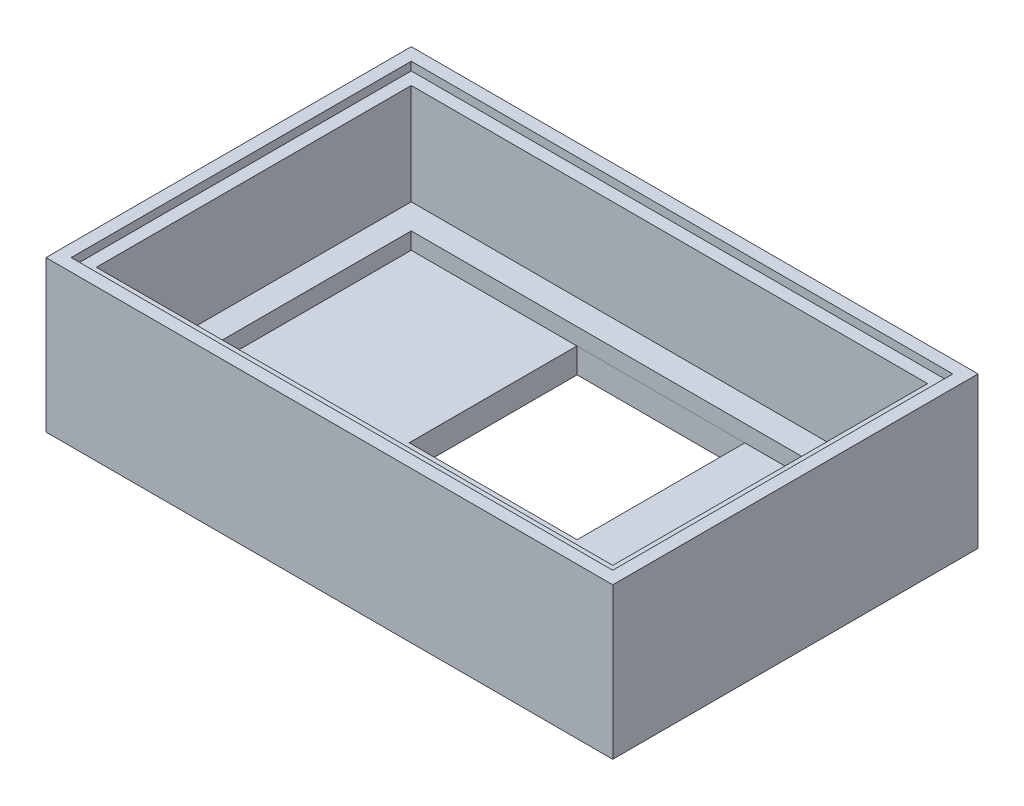
SolidWorks part; units mm, degrees
ref_plane "Спереди" through (0, 0, 0) normal (0, 0, 1) x (1, 0, 0)
ref_plane "Сверху" through (0, 0, 0) normal (0, 1, 0) x (1, 0, 0)
ref_plane "Справа" through (0, 0, 0) normal (1, 0, 0) x (0, 0, -1)
sketch "Эскиз1" plane through (0, 0, 0) normal (0, 1, 0) x (1, 0, 0)
  line L0 (-62.1873, 2.9179) -> (5.3127, 2.9179)
  line L1 (-59.1873, -0.0821) -> (2.3127, -0.0821)
  line L2 (-59.1873, -0.0821) -> (-59.1873, -37.5821)
  line L3 (-59.1873, -37.5821) -> (2.3127, -37.5821)
  line L4 (2.3127, -0.0821) -> (2.3127, -37.5821)
  line L5 (5.3127, 2.9179) -> (5.3127, -40.5821)
  line L6 (-62.1873, -40.5821) -> (5.3127, -40.5821)
  line L7 (-62.1873, 2.9179) -> (-62.1873, -40.5821)
  line L8 (-56.1873, -3.0821) -> (-0.6873, -3.0821)
  line L9 (-0.6873, -3.0821) -> (-0.6873, -36.0821)
  line L10 (-56.1873, -36.0821) -> (-0.6873, -36.0821)
  line L11 (-56.1873, -3.0821) -> (-56.1873, -36.0821)
  line L13 (2.3127, -37.5821) -> (-5.1873, -37.5821) construction
  line L14 (2.3127, -37.5821) -> (2.3127, -35.0321) construction
  line L15 (2.3127, -35.0321) -> (-5.1873, -35.0321) construction
  line L16 (-5.1873, -37.5821) -> (-5.1873, -35.0321) construction
  line L17 (-5.1873, -35.0321) -> (-9.6873, -35.0321)
  line L18 (-5.1873, -35.0321) -> (-5.1873, -30.5321)
  line L19 (-5.1873, -30.5321) -> (-9.6873, -30.5321)
  line L20 (-9.6873, -35.0321) -> (-9.6873, -30.5321)
  dimension "D1" = 3
extrude "Бобышка-Вытянуть2" add sketch "Эскиз1" along normal blind 2 contours L8 L9 L10 L11 | L2 L3 L4 L1
extrude "Бобышка-Вытянуть3" add sketch "Эскиз1<4>" along normal blind 15 contours L7 L6 L5 L0 | L2 L3 L4 L1
sketch "Эскиз1<4>" plane through (0, 0, 0) normal (0, 1, 0) x (1, 0, 0) same geometry as "Эскиз1"
extrude "Бобышка-Вытянуть4" add sketch "Эскиз1<5>" against normal blind 3 contours L6 L5 L0 L7
sketch "Эскиз1<5>" plane through (0, 0, 0) normal (0, 1, 0) x (1, 0, 0) same geometry as "Эскиз1"
extrude "Вырез-Вытянуть1" cut sketch "Эскиз1<6>" against normal up to next contours L20 L17 L18 L19 region at (-7.4373, 0, 32.7821)
sketch "Эскиз1<6>" plane through (0, 0, 0) normal (0, 1, 0) x (1, 0, 0) same geometry as "Эскиз1"
sketch "Эскиз3" plane through (0, 15, 0) normal (0, 1, 0) x (1, 0, 0)
  line L8 (-60.6873, -39.0821) -> (3.8127, -39.0821)
  line L9 (3.8127, -39.0821) -> (3.8127, 1.4179)
  line L10 (-60.6873, 1.4179) -> (-60.6873, -39.0821)
  line L11 (3.8127, 1.4179) -> (-60.6873, 1.4179)
  line L12 (-60.6873, -39.0821) -> (3.8127, -39.0821)
  line L13 (3.8127, -39.0821) -> (3.8127, 1.4179)
  line L14 (-60.6873, 1.4179) -> (-60.6873, -39.0821)
  line L15 (3.8127, 1.4179) -> (-60.6873, 1.4179)
  dimension "D1" = 1.5
extrude "Вырез-Вытянуть2" cut sketch "Эскиз3" against normal blind 1
sketch "Эскиз4" plane through (0, 0, 0) normal (0, 1, 0) x (1, 0, 0)
  line L0 (-37.4582, -19.5821) -> (49962.5418, -19.5821) construction
  line L1 (-36.4582, -3.0547) -> (-16.4582, -3.0547)
  line L2 (-36.4582, -3.0547) -> (-36.4582, -23.0547)
  line L3 (-36.4582, -23.0547) -> (-16.4582, -23.0547)
  line L4 (-16.4582, -3.0547) -> (-16.4582, -23.0547)
  line L5 (-56.1873, -3.0821) -> (-56.1873, -36.0821) construction
  line L6 (-32.767, -19.5821) -> (49967.233, -19.5821) construction
  point P8 (-56.1873, -19.5821)
extrude "Вырез-Вытянуть4" cut sketch "Эскиз4" against normal through all
